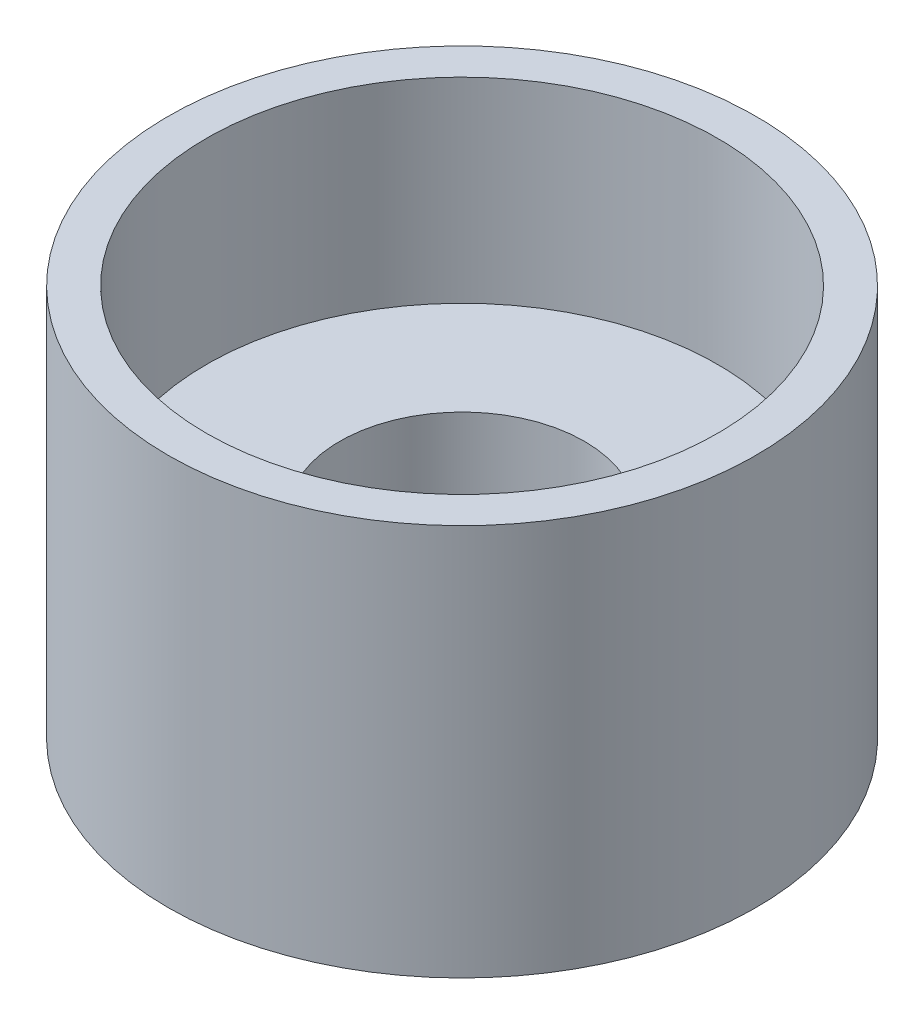
SolidWorks part; units mm, degrees
ref_plane "Front Plane" through (0, 0, 0) normal (0, 0, 1) x (1, 0, 0)
ref_plane "Top Plane" through (0, 0, 0) normal (0, 1, 0) x (1, 0, 0)
ref_plane "Right Plane" through (0, 0, 0) normal (1, 0, 0) x (0, 0, -1)
sketch "Sketch1" plane through (0, 0, 0) normal (0, 1, 0) x (1, 0, 0)
  circle A0 centre (0, 0) radius 38.1
  dimension "D1" = 76.2
extrude "Boss-Extrude2" add sketch "Sketch1" along normal blind 50.8
sketch "Sketch3" plane through (0, 50.8, 0) normal (0, 1, 0) x (1, 0, 0)
  circle A0 centre (0, 0) radius 33.147
  circle A1 centre (0, 0) radius 15.875
  dimension "D1" = 31.75
  dimension "D2" = 66.294
extrude "Cut-Extrude2" cut sketch "Sketch3" against normal blind 47.752 contours A1
extrude "Cut-Extrude3" cut sketch "Sketch3<6>" against normal blind 25.4
sketch "Sketch3<6>" plane through (0, 50.8, 0) normal (0, 1, 0) x (1, 0, 0) same geometry as "Sketch3"
sketch "Sketch4" plane through (0, 0, 0) normal (0, -1, 0) x (-1, 0, 0)
  circle A0 centre (0, 0) radius 9.525
  dimension "D1" = 19.05
extrude "Cut-Extrude4" cut sketch "Sketch4" against normal up to surface (3.048 mm away) up to face at (0, 3.048, 15.875)
